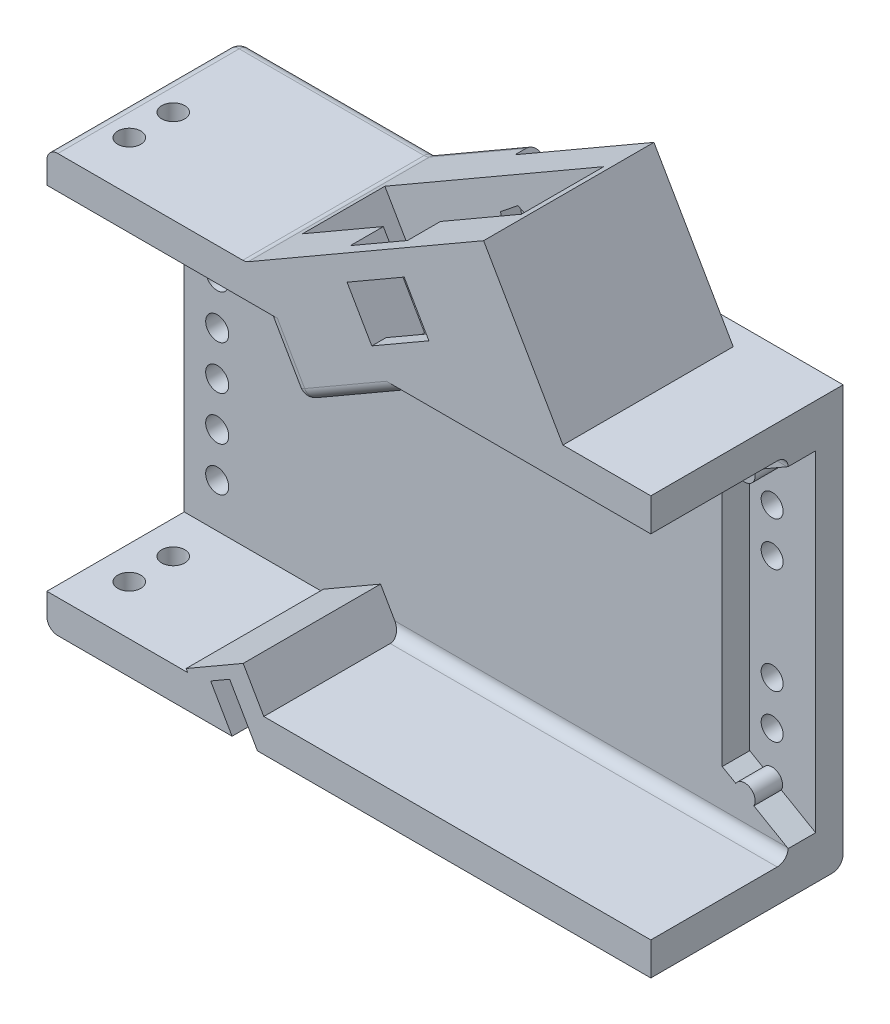
SolidWorks part; units mm, degrees
material "ABS"
ref_plane "前基準面" through (0, 0, 0) normal (0, 0, 1) x (1, 0, 0)
ref_plane "上基準面" through (0, 0, 0) normal (0, 1, 0) x (1, 0, 0)
ref_plane "右基準面" through (0, 0, 0) normal (1, 0, 0) x (0, 0, -1)
sketch "草圖2" plane through (0, 0, 0) normal (0, 0, 1) x (1, 0, 0)
  line L1 (-42.4346, 62.0442) -> (67.4854, 62.0442)
  line L2 (-42.4346, 62.0442) -> (-42.4346, -13.9558)
  line L3 (-42.4346, -13.9558) -> (67.4854, -13.9558)
  line L4 (67.4854, 62.0442) -> (67.4854, -13.9558)
  dimension "D1" = 109.92
  dimension "D2" = 76
extrude "填料-伸長1" add sketch "草圖2" along normal blind 10
sketch "草圖3" plane through (0, 0, 10) normal (0, 0, 1) x (1, 0, 0)
  line L0 (67.4854, 54.1442) -> (67.4854, -6.0558)
  line L1 (67.4854, -13.9558) -> (67.4854, 62.0442) construction
  line L2 (67.4854, 62.0442) -> (-42.4346, 62.0442) construction
  line L3 (67.4854, 54.1442) -> (55.4854, 47.2142)
  line L4 (55.4854, 47.2142) -> (55.4854, 0.8742)
  line L5 (55.4854, 0.8742) -> (67.4854, -6.0558)
  circle A0 centre (59.5654, 49.6442) radius 1.9
  circle A1 centre (59.5654, -1.5558) radius 1.9
  line M6 (67.4854, -13.9558) -> (67.4854, 62.0442)
  dimension "D7" = 7.92
  dimension "D8" = 7.92
  dimension "D9" = 3.8
  dimension "D10" = 3.8
  dimension "D12" = 12.4
  dimension "D1" = 60.2
  dimension "D2" = 7.9
  dimension "D3" = 12
  dimension "D4" = 12
  dimension "D5" = 46.34
  dimension "D6" = 6.93
  dimension "D11" = 51.2
extrude "除料-伸長1" cut sketch "草圖3" against normal blind 5 contours A1 L5 L3 A0 L4 M6
sketch "草圖4" plane through (0, 0, 5) normal (0, 0, 1) x (1, 0, 0)
  line L0 (67.4854, -6.0558) -> (67.4854, 54.1442) construction
  circle A0 centre (59.5654, 41.6442) radius 2
  circle A2 centre (59.5654, 33.6442) radius 2
  circle A3 centre (59.5654, 6.4442) radius 2
  circle A5 centre (59.5654, 14.4442) radius 2
  arc A6 (57.953, -0.5508) -> (61.2418, -2.4501) centre (59.5654, -1.5558) ccw construction
  dimension "D1" = 7.92
  dimension "D2" = 7.92
  dimension "D3" = 4
  dimension "D5" = 4
  dimension "D7" = 8
  dimension "D8" = 2
extrude "除料-伸長2" cut sketch "草圖4" against normal through all
sketch "草圖5" plane through (0, 0, 10) normal (0, 0, 1) x (1, 0, 0)
  line L0 (67.4854, -13.9558) -> (67.4854, -6.0558) construction
  line L1 (-42.4346, -13.9558) -> (67.4854, -13.9558)
  line L2 (-42.4346, -13.9558) -> (-42.4346, -7.9558)
  line L3 (-42.4346, -7.9558) -> (67.4854, -7.9558)
  line L4 (67.4854, -13.9558) -> (67.4854, -7.9558)
  line L5 (-42.4346, 62.0442) -> (-42.4346, -13.9558) construction
  line L6 (67.4854, 62.0442) -> (-42.4346, 62.0442)
  line L7 (67.4854, 62.0442) -> (67.4854, 56.0442)
  line L8 (67.4854, 56.0442) -> (-42.4346, 56.0442)
  line L9 (-42.4346, 62.0442) -> (-42.4346, 56.0442)
  dimension "D1" = 6
  dimension "D2" = 6
extrude "填料-伸長2" add sketch "草圖5" along normal blind 25
sketch "草圖7" plane through (0, -7.9558, 0) normal (0, 1, 0) x (1, 0, 0)
  line L0 (67.4854, -10) -> (-42.4346, -10) construction
  line L1 (-42.4346, -35) -> (-42.4346, -10) construction
  circle A0 centre (-36.4346, -18) radius 2.1
  circle A1 centre (-36.4346, -26) radius 2.1
  dimension "D1" = 4.2
  dimension "D2" = 8
  dimension "D4" = 6
  dimension "D3" = 2
extrude "除料-伸長3" cut sketch "草圖7" against normal through all both and the other way through all
sketch "草圖9" plane through (0, 0, 10) normal (0, 0, 1) x (1, 0, 0)
  line L2 (-42.4346, 56.0442) -> (-42.4346, -7.9558) construction
  line L3 (67.4854, -7.9558) -> (-42.4346, -7.9558) construction
  circle A0 centre (-36.4346, 0.0442) radius 2.1
  circle A1 centre (-36.4346, 8.0442) radius 2.1
  circle A2 centre (-36.4346, 16.0442) radius 2.1
  circle A3 centre (-36.4346, 24.0442) radius 2.1
  circle A4 centre (-36.4346, 32.0442) radius 2.1
  circle A5 centre (-36.4346, 40.0442) radius 2.1
  circle A6 centre (-36.4346, 48.0442) radius 2.1
  dimension "D1" = 6
  dimension "D2" = 4.2
  dimension "D3" = 8
  dimension "D4" = 7
extrude "除料-伸長4" cut sketch "草圖9" against normal through all
sketch "草圖10" plane through (0, 0, 0) normal (0, 0, -1) x (-1, 0, 0)
  line L0 (36.4346, 0.0442) -> (36.4346, 48.0442) construction
  line L1 (32.4346, 0.0442) -> (32.4346, 48.0442)
  line L2 (40.4346, 0.0442) -> (40.4346, 48.0442)
  arc A0 (32.4346, 0.0442) -> (40.4346, 0.0442) centre (36.4346, 0.0442) ccw
  arc A1 (40.4346, 48.0442) -> (32.4346, 48.0442) centre (36.4346, 48.0442) ccw
  point P4 (36.4346, 24.0442)
  dimension "D1" = 8
extrude "除料-伸長5" cut sketch "草圖10" against normal blind 5
sketch "草圖11" plane through (0, 0, 35) normal (0, 0, 1) x (1, 0, 0)
  line L0 (51.4854, 62.0442) -> (37.0517, 87.0442)
  line L1 (67.4854, 62.0442) -> (-42.4346, 62.0442) construction
  line L2 (37.0517, 87.0442) -> (-6.2496, 62.0442)
  line L3 (-6.2496, 62.0442) -> (51.4854, 62.0442)
  line L4 (67.4854, 56.0442) -> (67.4854, 62.0442) construction
  dimension "D1" = 30
  dimension "D2" = 270
  dimension "D3" = 50
  dimension "D4" = 16
extrude "填料-伸長3" add sketch "草圖11" along direction (0, 0, 1) on the side against the normal through all
sketch "草圖12" plane through (0, 0, 35) normal (0, 0, 1) x (1, 0, 0)
  line L0 (-6.2496, 62.0442) -> (37.0517, 87.0442)
  line L1 (-6.2496, 62.0442) -> (3.7504, 44.7237)
  line L2 (37.0517, 87.0442) -> (47.0517, 69.7237)
  line L3 (3.7504, 44.7237) -> (47.0517, 69.7237)
  dimension "D1" = 20
extrude "填料-伸長4" add sketch "草圖12" along direction (0, 0, 1) on the side against the normal up to next (35 mm away)
sketch "草圖13" plane through (-28.4283, 49.2393, 0) normal (-0.5, 0.866, 0) x (0.866, 0.5, 0)
  line L1 (73.6098, -26.4) -> (27.6098, -26.4)
  line L2 (73.6098, -26.4) -> (73.6098, -11.4)
  line L3 (73.6098, -11.4) -> (27.6098, -11.4)
  line L4 (27.6098, -26.4) -> (27.6098, -11.4)
  line L6 (75.6098, 0) -> (75.6098, -35) construction
  line L8 (56.6098, -26.4) -> (44.6098, -26.4)
  line L9 (56.6098, -26.4) -> (56.6098, -32.4)
  line L10 (56.6098, -32.4) -> (44.6098, -32.4)
  line L11 (44.6098, -26.4) -> (44.6098, -32.4)
  dimension "D1" = 15
  dimension "D2" = 12.5
  dimension "D3" = 46
  dimension "D4" = 2
  dimension "D5" = 12
  dimension "D6" = 17
  dimension "D7" = 21
extrude "除料-伸長6" cut sketch "草圖13" against normal blind 15 contours L4 L1 L2 L3 | L1 L11 L10 L9
sketch "草圖14" plane through (0, 0, 32.4) normal (0, 0, -1) x (-1, 0, 0)
  line L4 (-22.5972, 74.0801) -> (-27.0972, 66.2858)
  line L5 (-22.5972, 74.0801) -> (-12.2049, 68.0801)
  line L6 (-27.0972, 66.2858) -> (-16.7049, 60.2858)
  line L7 (-12.2049, 68.0801) -> (-16.7049, 60.2858)
  line L8 (-28.0972, 64.5538) -> (-20.5972, 77.5442) construction
  line L10 (-28.0972, 64.5538) -> (-17.7049, 58.5538) construction
  line L11 (-17.7049, 58.5538) -> (-10.2049, 71.5442) construction
  dimension "D1" = 2
  dimension "D2" = 0
  dimension "D3" = 9
extrude "除料-伸長7" cut sketch "草圖14" against normal blind 15
sketch "草圖15" plane through (-20.9283, 36.2489, 0) normal (-0.5, 0.866, 0) x (0.866, 0.5, 0)
  line L2 (27.6098, -26.4) -> (27.6098, -11.4) construction
  line L4 (73.6098, -11.4) -> (27.6098, -11.4) construction
  circle A0 centre (69.1098, -18.9) radius 1.25
  circle A1 centre (32.1098, -18.9) radius 1.25
  dimension "D1" = 37
  dimension "D2" = 4.5
  dimension "D3" = 7.5
  dimension "D4" = 2.5
  dimension "D5" = 2.5
  dimension "D6" = 7.5
extrude "除料-伸長8" cut sketch "草圖15" along direction (0.5, -0.866, 0) on the side against the normal up to next (28.7095 mm away)
sketch "草圖18" plane through (0, 0, 35) normal (0, 0, 1) x (1, 0, 0)
  line L0 (-13.3436, -13.9558) -> (-13.5936, -13.5228)
  line L1 (-42.4346, -13.9558) -> (67.4854, -13.9558) construction
  line L2 (-13.5936, -13.5228) -> (-10.1295, -11.5228)
  line L3 (-10.1295, -11.5228) -> (-8.7248, -13.9558)
  line L4 (-8.7248, -13.9558) -> (-13.3436, -13.9558)
  line L5 (-4.106, -13.9558) -> (-6.6654, -9.5228)
  line L6 (-6.6654, -9.5228) -> (-3.2013, -7.5228)
  line L7 (-3.2013, -7.5228) -> (0.5128, -13.9558)
  line L8 (0.5128, -13.9558) -> (-4.106, -13.9558)
  line L9 (-13.5936, -13.5228) -> (-3.2013, -7.5228)
  line L10 (-13.5936, -13.5228) -> (-17.0936, -7.4606)
  line L11 (-3.2013, -7.5228) -> (-6.7013, -1.4606)
  line L12 (-17.0936, -7.4606) -> (-6.7013, -1.4606)
  line M9 (67.4854, -7.9558) -> (-42.4346, -7.9558)
  line M13 (-42.4346, -13.9558) -> (67.4854, -13.9558)
  dimension "D1" = 60
  dimension "D2" = 70
  dimension "D3" = 4
  dimension "D4" = 0.5
  dimension "D5" = 60
  dimension "D6" = 4
  dimension "D7" = 0
  dimension "D8" = 4
  dimension "D9" = 7
extrude "填料-伸長5" add sketch "草圖18" against normal up to surface (35 mm away) contours L7 L6 M13 | L2 L3 L0 M13 | L5 L6 M13 | L12 L10 L6 L11 M13 M9 | L12 L11 M9
sketch "草圖21" plane through (0, 0, 0) normal (0, 0, -1) x (-1, 0, 0)
  line L1 (-37.0517, 87.0442) -> (-43.0517, 76.6519)
  line L5 (-43.0517, 76.6519) -> (-51.4854, 62.0442)
  line L6 (-51.4854, 62.0442) -> (-17.7504, 62.0442)
  line L8 (-17.7504, 62.0442) -> (-11.7504, 72.4365)
  line L9 (-37.0517, 87.0442) -> (6.2496, 62.0442) construction
  line L10 (-11.7504, 72.4365) -> (-37.0517, 87.0442)
  line L11 (6.2496, 62.0442) -> (-17.7504, 62.0442)
  dimension "D1" = 12
  dimension "D2" = 180
extrude "除料-伸長10" cut sketch "草圖21" against normal blind 4
sketch "草圖22" plane through (0, 0, 4) normal (0, 0, -1) x (-1, 0, 0)
  line L2 (-37.0517, 87.0442) -> (-51.4854, 62.0442) construction
  line L3 (-11.7504, 72.4365) -> (-37.0517, 87.0442) construction
  circle A0 centre (-34.1235, 76.116) radius 2
  circle A1 centre (-20.2671, 68.116) radius 2
  dimension "D1" = 8
  dimension "D2" = 2
  dimension "D3" = 4
  dimension "D4" = 8
extrude "除料-伸長11" cut sketch "草圖22" against normal up to next
sketch "草圖23" plane through (0, 0, 11.4) normal (0, 0, 1) x (1, 0, 0)
  line L0 (16.5396, 69.5671) -> (17.1466, 65.6134)
  line L1 (30.396, 77.5671) -> (31.003, 73.6134)
  line L2 (31.003, 73.6134) -> (34.7305, 72.1623)
  line L3 (34.7305, 72.1623) -> (37.851, 74.6648)
  line L4 (37.851, 74.6648) -> (37.244, 78.6185)
  line L5 (37.244, 78.6185) -> (33.5165, 80.0696)
  line L6 (33.5165, 80.0696) -> (30.396, 77.5671)
  line L7 (17.1466, 65.6134) -> (20.8741, 64.1623)
  line L8 (20.8741, 64.1623) -> (23.9946, 66.6648)
  line L9 (23.9946, 66.6648) -> (23.3876, 70.6185)
  line L10 (23.3876, 70.6185) -> (19.6601, 72.0696)
  line L11 (19.6601, 72.0696) -> (16.5396, 69.5671)
  circle A0 centre (34.1235, 76.116) radius 4 construction
  circle A1 centre (20.2671, 68.116) radius 4 construction
  dimension "D1" = 8
  dimension "D2" = 2
extrude "除料-伸長12" cut sketch "草圖23" against normal blind 3.5
sketch "草圖24" plane through (0, 0, 35) normal (0, 0, 1) x (1, 0, 0)
  line L0 (-7.5701, -15.9558) -> (-4.106, -13.9558)
  line L1 (-7.5701, -15.9558) -> (-12.6295, -7.1927)
  line L2 (-4.106, -13.9558) -> (-9.1654, -5.1927)
  line L3 (-12.6295, -7.1927) -> (-9.1654, -5.1927)
  line L4 (-17.0936, -7.4606) -> (-6.7013, -1.4606) construction
  line L5 (-42.4346, -13.9558) -> (67.4854, -13.9558) construction
  line L7 (-16.8077, -7.9558) -> (-17.0936, -7.4606) construction
  dimension "D1" = 2
  dimension "D2" = 4
  dimension "D3" = 4
extrude "除料-伸長14" cut sketch "草圖24" against normal up to next
sketch "草圖25" plane through (0, 0, 0) normal (0, 0, -1) x (-1, 0, 0)
  line L0 (8.7248, -13.9558) -> (4.106, -13.9558)
  line L1 (4.106, -13.9558) -> (9.1654, -5.1927)
  line L2 (9.1654, -5.1927) -> (12.6295, -7.1927)
  line L3 (12.6295, -7.1927) -> (8.7248, -13.9558)
extrude "填料-伸長6" add sketch "草圖25" against normal blind 3
fillet "圓角1" radius 2 17 edges at (67.4854, 55.0942, 10) (-24.3421, 62.0442, 0) (-6.2496, 62.0442, 17.5) (45.4218, 56.0442, 10) (0.4825, 50.3839, 10) (13.5543, 50.3839, 10) (3.7504, 44.7237, 22.5) (0.4825, 50.3839, 35) (13.5543, 50.3839, 35) (2.7504, 67.2403, 0) (67.4854, -7.0058, 10) (12.5254, -13.9558, 0) (32.2671, -7.9558, 10) (-42.4346, 24.0442, 0) (-22.61, 56.0442, 10) (-42.4346, 62.0442, 17.5) (-42.4346, -13.9558, 17.5)
